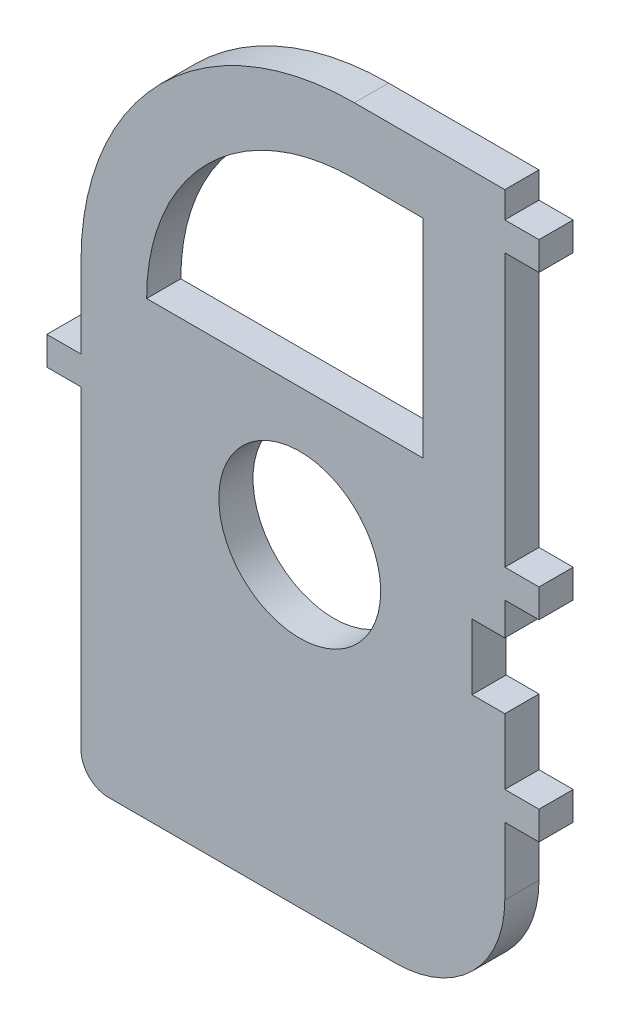
SolidWorks part; units mm, degrees
material "Balsa"
ref_plane "Front Plane" through (0, 0, 0) normal (0, 0, 1) x (1, 0, 0)
ref_plane "Top Plane" through (0, 0, 0) normal (0, 1, 0) x (1, 0, 0)
ref_plane "Right Plane" through (0, 0, 0) normal (1, 0, 0) x (0, 0, -1)
sketch "Sketch1" plane through (0, 0, 0) normal (0, 0, 1) x (1, 0, 0)
  line L0 (0, -1000.1535) -> (0, 48999.8465) construction
  line L2 (-1000, 0) -> (49000, 0) construction
  line L3 (9.525, 16.51) -> (11.1125, 16.51)
  line L4 (2.54, 19.05) -> (9.525, 19.05)
  line L5 (-10.16, 6.35) -> (-10.16, -14.605)
  line L6 (-10.16, -14.605) -> (9.525, -14.605)
  line L7 (9.525, 19.05) -> (9.525, -14.605)
  line L8 (-11.7475, 1.27) -> (-10.16, 1.27)
  line L9 (-11.7475, 1.27) -> (-11.7475, 2.5908)
  line L10 (-11.7475, 2.5908) -> (-10.16, 2.5908)
  line L11 (-10.16, 1.27) -> (-10.16, 2.5908)
  line L12 (9.525, 2.54) -> (11.1125, 2.54)
  line L13 (9.525, 2.54) -> (9.525, 3.8608)
  line L14 (9.525, 3.8608) -> (11.1125, 3.8608)
  line L15 (11.1125, 2.54) -> (11.1125, 3.8608)
  line L16 (9.525, 16.51) -> (9.525, 17.8308)
  line L17 (9.525, 17.8308) -> (11.1125, 17.8308)
  line L18 (11.1125, 16.51) -> (11.1125, 17.8308)
  line L19 (9.525, -5.08) -> (11.1125, -5.08)
  line L20 (9.525, -5.08) -> (9.525, -6.4008)
  line L21 (9.525, -6.4008) -> (11.1125, -6.4008)
  line L22 (11.1125, -5.08) -> (11.1125, -6.4008)
  line L27 (9.525, 1.016) -> (8.001, 1.016)
  line L28 (9.525, 1.016) -> (9.525, -2.032)
  line L29 (9.525, -2.032) -> (8.001, -2.032)
  line L30 (8.001, 1.016) -> (8.001, -2.032)
  circle A0 centre (0, 0) radius 3.7592
  arc A3 (2.54, 19.05) -> (-10.16, 6.35) centre (2.54, 6.35) ccw
  dimension "D1" = 7.5184
  dimension "D4" = 14.605
  dimension "D3" = 16.51
  dimension "D5" = 1.5875
  dimension "D9" = 12.7
  dimension "D10" = 1.5875
  dimension "D18" = 1.27
  dimension "D2" = 19.05
  dimension "D6" = 9.525
  dimension "D7" = 1.3208
  dimension "D8" = 19.685
  dimension "D11" = 2.54
  dimension "D12" = 1.3208
  dimension "D13" = 1.3208
  dimension "D14" = 1.5875
  dimension "D15" = 1.524
  dimension "D16" = 1.016
  dimension "D17" = 3.048
  dimension "D19" = 1.5875
  dimension "D20" = 1.3208
  dimension "D21" = 5.08
extrude "Boss-Extrude1" add sketch "Sketch1" along normal blind 1.5875 contours L4 A3 L5 L6 L7 A0 | L10 L9 L8 L5 | L3 L18 L17 L7 | L12 L15 L14 L7 | A3 L5 | L22 L19 L7 L21 region at (10.3187, 17.1704, 0) region at (9.1351, 10.1854, 0) region at (10.3187, 3.2004, 0) region at (-10.9538, 1.9304, 0) region at (10.3187, -5.7404, 0)
fillet "Fillet1" radius 5.08 1 edges at (9.525, -14.605, 0.7937)
fillet "Fillet2" radius 1.27 1 edges at (-10.16, -14.605, 0.7937)
sketch "Sketch2" plane through (0, 0, 1.5875) normal (0, 0, 1) x (1, 0, 0)
  line L0 (-7.112, 6.35) -> (5.715, 6.35)
  line L1 (5.715, 16.002) -> (2.54, 16.002)
  line L2 (5.715, 16.002) -> (5.715, 6.35)
  line L3 (9.525, 16.51) -> (9.525, 3.8608) construction
  arc A2 (2.54, 16.002) -> (-7.112, 6.35) centre (2.54, 6.35) ccw
  arc A3 (2.54, 16.002) -> (-7.112, 6.35) centre (2.54, 6.35) ccw
  dimension "D2" = 3.81
  dimension "D1" = 3.048
extrude "Weight Reduction" cut sketch "Sketch2" against normal up to next
